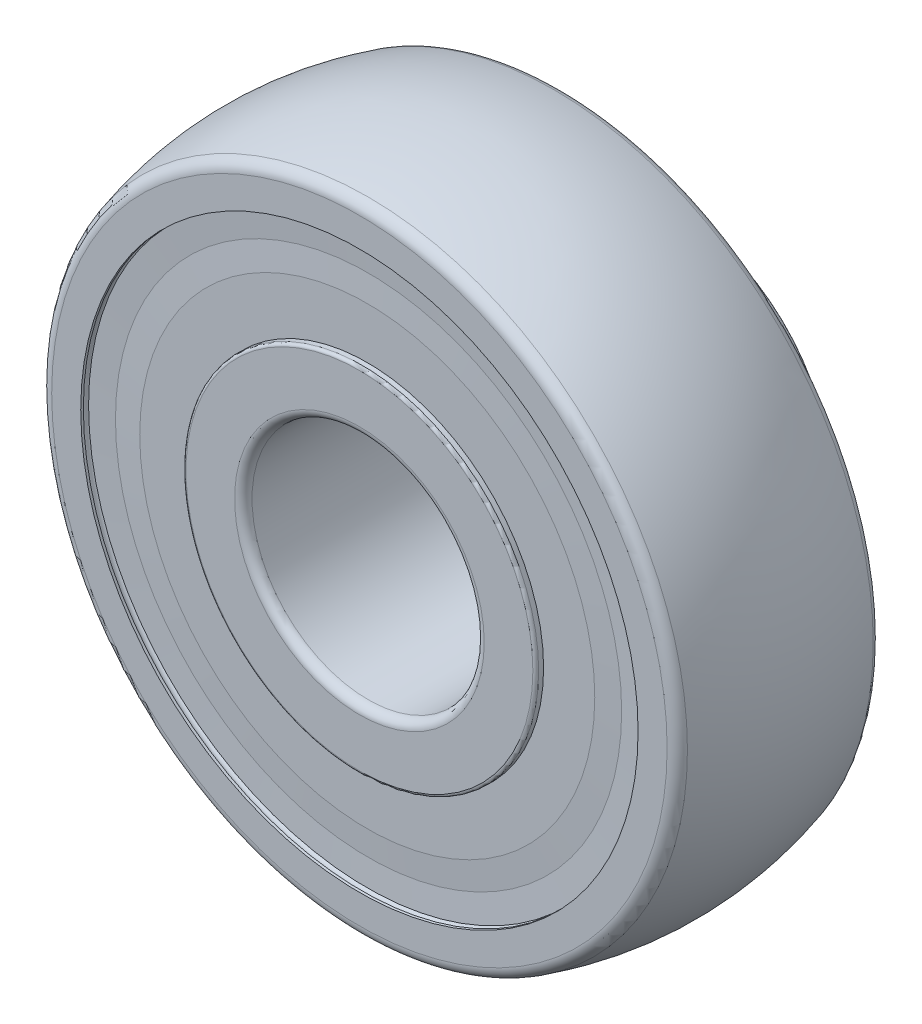
SolidWorks part; units mm, degrees
ref_plane "Front Plane" through (0, 0, 0) normal (0, 0, 1) x (1, 0, 0)
ref_plane "Top Plane" through (0, 0, 0) normal (0, 1, 0) x (1, 0, 0)
ref_plane "Right Plane" through (0, 0, 0) normal (1, 0, 0) x (0, 0, -1)
sketch "Sketch1" plane through (0, 0, 0) normal (1, 0, 0) x (0, 0, -1)
  line L0 (-3.2, 4) -> (3.2, 4)
  line L1 (0, 9.3345) -> (0, 11) construction
  line L2 (3.5, 5.975) -> (3.5, 5.55)
  line L3 (0, 0) -> (0, 4) construction
  line L4 (-3.5, 0) -> (3.5, 0) construction
  line L5 (-1.5207, 6.075) -> (-3.14, 6.075)
  line L6 (-3.5, 5.975) -> (-3.5, 4.3)
  line L7 (0, 4) -> (0, 5.3655) construction
  line L8 (-3.14, 6.075) -> (-3.05, 7.8375)
  line L9 (-3.05, 7.8375) -> (-3.05, 8.7188)
  line L10 (-3.05, 8.7188) -> (-3.14, 9.6)
  line L11 (-3.14, 9.6) -> (-3.23, 9.6)
  line L12 (-3.23, 9.6) -> (-3.185, 8.7188)
  line L13 (-3.185, 8.7188) -> (-3.23, 7.8375)
  line L14 (-3.23, 7.8375) -> (-3.23, 6.075)
  line L15 (-3.23, 6.075) -> (-3.4, 6.075)
  line L16 (3.23, 6.075) -> (3.4, 6.075)
  line L17 (3.23, 7.8375) -> (3.23, 6.075)
  line L18 (3.185, 8.7188) -> (3.23, 7.8375)
  line L19 (3.23, 9.6) -> (3.185, 8.7188)
  line L20 (3.14, 9.6) -> (3.23, 9.6)
  line L21 (3.05, 8.7188) -> (3.14, 9.6)
  line L22 (3.05, 7.8375) -> (3.05, 8.7188)
  line L23 (3.14, 6.075) -> (3.05, 7.8375)
  line L24 (1.5207, 6.075) -> (3.14, 6.075)
  line L25 (-3.5, 9.6) -> (-3.5, 10.6003)
  line L26 (-3.2, 11) -> (3.2, 11) construction
  line L27 (3.5, 9.6) -> (3.5, 10.6003)
  line L28 (3.41, 9.6) -> (3.5, 9.6)
  line L29 (2.9089, 8.8) -> (3.05, 9.6)
  line L30 (1.3549, 8.8) -> (2.9089, 8.8)
  line L31 (-2.9089, 8.8) -> (-3.05, 9.6)
  line L32 (3.6, 5.45) -> (7.25, 5.45)
  line L33 (-3.41, 9.6) -> (-3.5, 9.6)
  line L34 (3.5, 5.45) -> (3.5, 4.3) construction
  line L35 (-1.3549, 8.8) -> (-2.9089, 8.8)
  line L36 (3.2, 4) -> (7.05, 4)
  line L37 (7.35, 4.3) -> (7.35, 5.35)
  line L38 (3.5, 5.55) -> (3.6, 5.45)
  line L39 (-3.5, 10.6003) -> (-3.5, 10.7) construction
  line L40 (3.5, 10.6003) -> (3.5, 10.7) construction
  arc A0 (-1.5207, 6.075) -> (1.5207, 6.075) centre (0, 7.35) ccw
  arc A1 (-3.5, 10.7) -> (-3.2, 11) centre (-3.2, 10.7) cw construction
  arc A2 (-3.4, 6.075) -> (-3.5, 5.975) centre (-3.4, 5.975) ccw
  arc A3 (3.2, 4) -> (3.5, 4.3) centre (3.2, 4.3) ccw construction
  arc A4 (-3.2, 4) -> (-3.5, 4.3) centre (-3.2, 4.3) cw
  arc A5 (-3.05, 9.6) -> (-3.41, 9.6) centre (-3.23, 9.6) ccw
  arc A6 (3.4, 6.075) -> (3.5, 5.975) centre (3.4, 5.975) cw
  arc A7 (1.3549, 8.8) -> (-1.3549, 8.8) centre (0, 7.35) ccw
  arc A8 (3.5, 10.7) -> (3.2, 11) centre (3.2, 10.7) ccw construction
  arc A9 (3.05, 9.6) -> (3.41, 9.6) centre (3.23, 9.6) cw
  arc A10 (7.05, 4) -> (7.35, 4.3) centre (7.05, 4.3) ccw
  arc A11 (7.25, 5.45) -> (7.35, 5.35) centre (7.25, 5.35) cw
  arc A12 (-3.2, 11) -> (3.2, 11) centre (0, 0) cw
  arc A13 (-3.2, 11) -> (-3.5, 10.6003) centre (-3.0837, 10.6003) ccw
  arc A14 (3.5, 10.6003) -> (3.2, 11) centre (3.0837, 10.6003) ccw
  point P16 (-3.5, 6.075)
  point P19 (3.5, 4)
  point P22 (-3.5, 4)
  point P65 (7.35, 5.45)
  dimension "D2" = 1.9845
  dimension "D6" = 3.5
  dimension "D7" = 0.3
  dimension "D12" = 0.1
  dimension "D18" = 0.18
  dimension "D22" = 3.85
  dimension "D1" = 8
  dimension "D3" = 7
  dimension "D4" = 12.15
  dimension "D5" = 14.7
  dimension "D8" = 0.045
  dimension "D9" = 0.18
  dimension "D10" = 0.09
  dimension "D11" = 0.09
  dimension "D13" = 6.46
  dimension "D14" = 15.675
  dimension "D15" = 17.4375
  dimension "D16" = 19.2
  dimension "D17" = 11
  dimension "D19" = 0.09
  dimension "D20" = 100
  dimension "D21" = 17.6
  dimension "D23" = 10.9
revolve "Bearing Body" add sketch "Sketch1" angle 360 about L4
ref_axis "Rotation Axis" through (0, 0, -7.05) along (0, 0, 1)
sketch "Sketch2" plane through (0, 0, 0) normal (1, 0, 0) x (0, 0, -1)
  line L0 (1.9845, 7.35) -> (-1.9845, 7.35)
  line L1 (0, 0) -> (0, 7.35) construction
  arc A0 (-1.9845, 7.35) -> (1.9845, 7.35) centre (0, 7.35) ccw
  arc A1 (-1.5207, 6.075) -> (1.5207, 6.075) centre (0, 7.35) ccw construction
  dimension "D1" = 3.969
revolve "Ball" add sketch "Sketch2" angle 360 about L0
pattern_circular "Ball Pattern" count 7 over 360 about axis through (0, 0, -7.05) along (0, 0, 1) of bodies 104
ref_plane "Set Screw Hole Plane" through (0, 5.45, 0) normal (0, 1, 0) x (1, 0, 0)
sketch "Set Screw Hole Reference" plane through (0, 5.45, 0) normal (0, 1, 0) x (1, 0, 0)
  line L0 (0, 3.5) -> (0, 5.425) construction
  line L2 (0, 5.425) -> (0, 7.35) construction
  line L3 (5.35, 7.35) -> (-5.35, 7.35) construction
  line L4 (5.55, 3.5) -> (-5.55, 3.5) construction
  line L5 (5.55, 3.5) -> (-5.55, 3.5) construction
  circle A0 centre (0, 5.425) radius 1.25 construction
  dimension "D1" = 2.5
hole_wizard "M3 Set Screw Hole" positions "Sketch7" profile "Sketch6" tap size "M3" standard "ISO"
sketch "Sketch7" plane through (0, 5.45, 0) normal (0, 1, 0) x (1, 0, 0)
  point P0 (0, 5.425)
sketch "Sketch6" plane through (0, 5.45, -5.425) normal (1, 0, 0) x (0, 0, 1)
  line L0 (0, 0) -> (0, 8.2511)
  line L1 (0, 8.2511) -> (1.25, 7.5)
  line L2 (1.25, 7.5) -> (1.25, 0)
  line L5 (1.25, 0) -> (0, 0)
  line L10 (0, 8.2511) -> (-1.25, 7.5) construction
  line L11 (0, -6.35) -> (0, 107.95) construction
  dimension "Tap Drill Dia." = 2.5
  dimension "Tap Drill Depth" = 7.5
  dimension "Drill Angle" = 118
pattern_circular "M3 Set Screw Hole Pattern" count 2 every 90 about axis through (0, 0, -7.05) along (0, 0, 1) of "M3 Set Screw Hole" reverse direction yes
